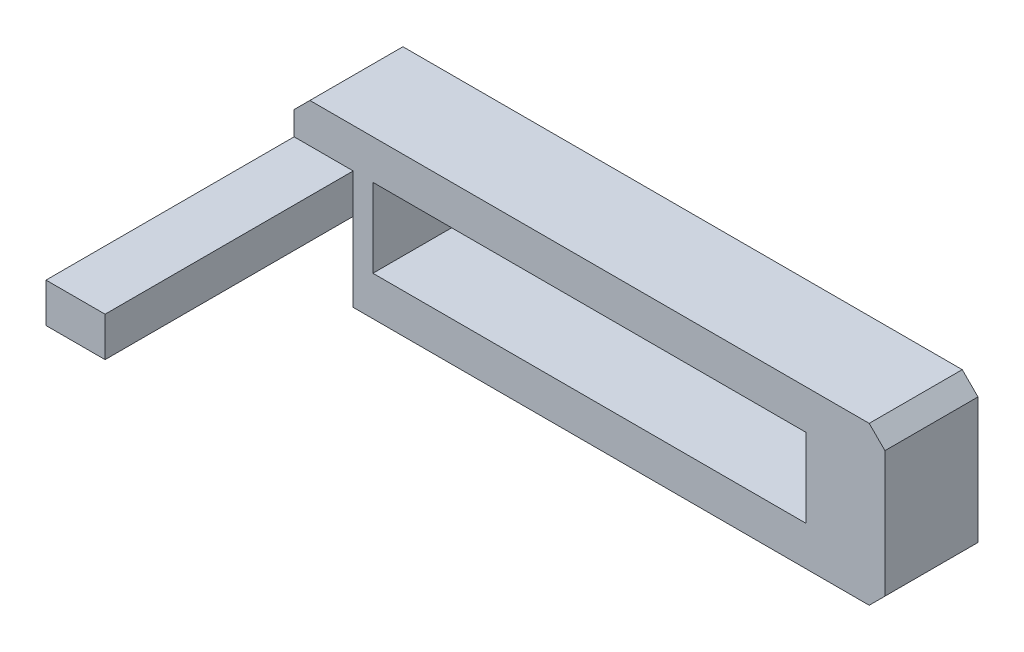
SolidWorks part; units mm, degrees
ref_plane "Front Plane" through (0, 0, 0) normal (0, 0, 1) x (1, 0, 0)
ref_plane "Top Plane" through (0, 0, 0) normal (0, 1, 0) x (1, 0, 0)
ref_plane "Right Plane" through (0, 0, 0) normal (1, 0, 0) x (0, 0, -1)
sketch "Sketch1" plane through (0, 0, 0) normal (0, 0, 1) x (1, 0, 0)
  line L1 (0, 0) -> (-95.25, 0)
  line L2 (0, 0) -> (0, 25.4)
  line L3 (0, 25.4) -> (-95.25, 25.4)
  line L4 (-95.25, 0) -> (-95.25, 25.4)
  line L5 (-12.7, 19.05) -> (-82.55, 19.05)
  line L6 (-12.7, 19.05) -> (-12.7, 6.35)
  line L7 (-12.7, 6.35) -> (-82.55, 6.35)
  line L8 (-82.55, 19.05) -> (-82.55, 6.35)
  point P9 (-47.625, 25.4)
  point P10 (-47.625, 6.35)
  point P11 (-12.7, 18.6405)
  dimension "D1" = 95.25
  dimension "D2" = 25.4
  dimension "D3" = 19.05
  dimension "D4" = 12.7
  dimension "D5" = 6.35
extrude "Boss-Extrude1" add sketch "Sketch1" along normal blind 15 contours L8 L3 L4 L1 L2 L6 L7 region at (-47.625, 0.9858, 0)
sketch "Sketch2" plane through (0, 0, 15) normal (0, 0, 1) x (1, 0, 0)
  line L0 (-95.25, 0) -> (-95.25, 25.4) construction
  line L1 (-95.25, 12.7) -> (-85.725, 12.7)
  line L2 (-95.25, 12.7) -> (-95.25, 19.05)
  line L3 (-95.25, 19.05) -> (-85.725, 19.05)
  line L4 (-85.725, 12.7) -> (-85.725, 19.05)
  line L5 (0, 0) -> (-95.25, 0) construction
  dimension "D1" = 9.525
  dimension "D2" = 6.35
  dimension "D3" = 12.7
extrude "Boss-Extrude2" add sketch "Sketch2" along normal blind 40
chamfer "Chamfer1" distance 2.54 angle 45 4 edges at (0, 0, 7.5) (-95.25, 0, 7.5) (0, 25.4, 7.5) (-95.25, 25.4, 7.5)
sketch "Sketch4" plane through (0, 0, 15) normal (0, 0, 1) x (1, 0, 0)
  line L0 (-95.25, 2.54) -> (-95.25, 12.7) construction
  line L1 (-85.725, 12.7) -> (-95.25, 12.7)
  line L2 (-85.725, 12.7) -> (-85.725, 0)
  line L3 (-85.725, 0) -> (-95.25, 0)
  line L4 (-95.25, 12.7) -> (-95.25, 0)
  line L5 (-2.54, 0) -> (-92.71, 0) construction
extrude "Cut-Extrude2" cut sketch "Sketch4" against normal through all
